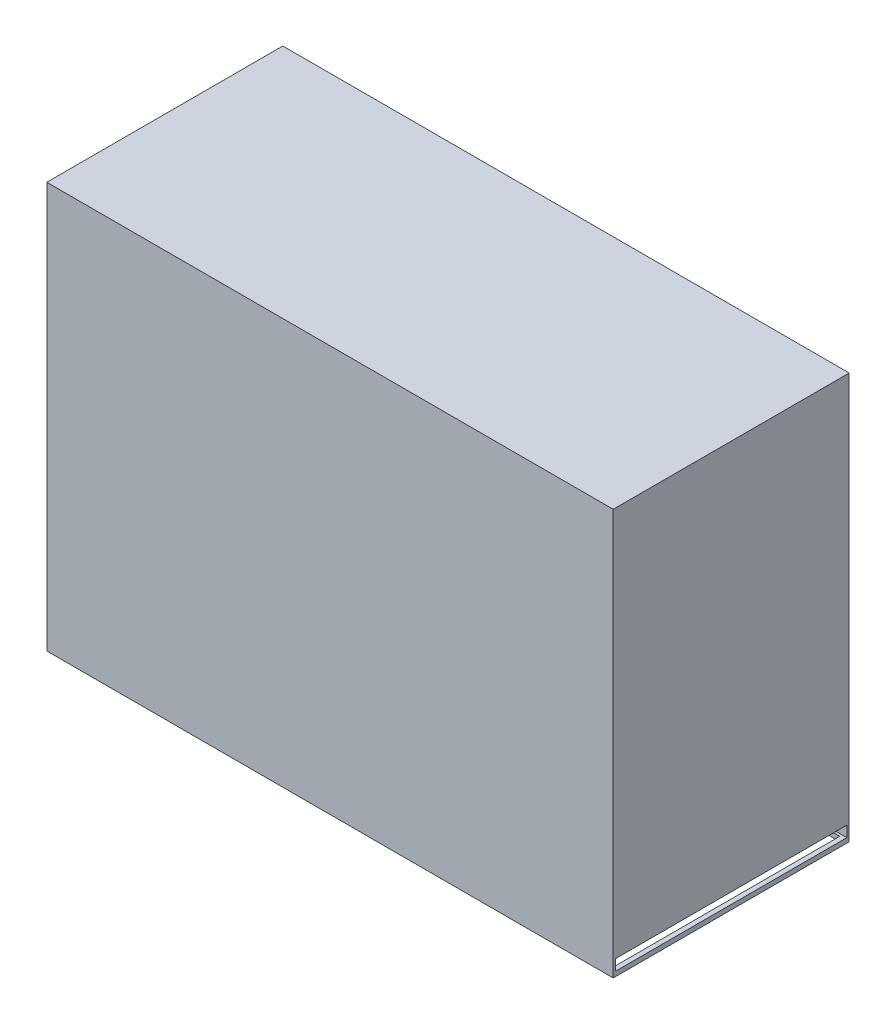
SolidWorks part; units mm, degrees
ref_plane "Piano frontale" through (0, 0, 0) normal (0, 0, 1) x (1, 0, 0)
ref_plane "Piano superiore" through (0, 0, 0) normal (0, 1, 0) x (1, 0, 0)
ref_plane "Piano destro" through (0, 0, 0) normal (1, 0, 0) x (0, 0, -1)
sketch "Schizzo1" plane through (0, 0, 0) normal (0, 0, 1) x (1, 0, 0)
  line L1 (0, 0) -> (120, 0)
  line L2 (0, 0) -> (0, 82)
  line L3 (0, 82) -> (120, 82)
  line L4 (120, 0) -> (120, 82)
  point P9 (0, 0)
  point P10 (0, 0)
  dimension "D1" = 120
  dimension "D2" = 82
extrude "Estrusione-Estrusione4" add sketch "Schizzo1" along normal blind 50
sketch "Schizzo6" plane through (0, 0, 0) normal (0, -1, 0) x (1, 0, 0)
  line L0 (0, 50) -> (120, 50) construction
  line L1 (1, 49) -> (119, 49)
  line L2 (1, 49) -> (1, 1)
  line L3 (1, 1) -> (119, 1)
  line L4 (119, 49) -> (119, 1)
  line L5 (0, 50) -> (0, 0) construction
  dimension "D1" = 48
  dimension "D2" = 118
  dimension "D3" = 1
  dimension "D4" = 1
extrude "Taglio-Estrusione2" cut sketch "Schizzo6" against normal blind 50
sketch "Schizzo7" plane through (0, 50, 0) normal (0, -1, 0) x (1, 0, 0)
  line L1 (1, 49) -> (54, 49)
  line L2 (1, 49) -> (1, 29)
  line L3 (1, 29) -> (54, 29)
  line L4 (54, 49) -> (54, 29)
  dimension "D1" = 53
  dimension "D2" = 20
extrude "Estrusione-Estrusione5" add sketch "Schizzo7" along normal blind 27
sketch "Schizzo8" plane through (0, 23, 0) normal (0, -1, 0) x (1, 0, 0)
  line L0 (1, 29) -> (54, 29) construction
  line L1 (1, 49) -> (53, 49)
  line L2 (1, 49) -> (1, 30)
  line L3 (1, 30) -> (53, 30)
  line L4 (53, 49) -> (53, 30)
  line L5 (54, 29) -> (54, 49) construction
  line L6 (1, 49) -> (1, 1) construction
  dimension "D1" = 19
  dimension "D2" = 1
  dimension "D3" = 1
  dimension "D4" = 0
extrude "Taglio-Estrusione4" cut sketch "Schizzo8" against normal blind 27 contours L2 L1 L4 L3
sketch "Schizzo9" plane through (0, 50, 0) normal (0, -1, 0) x (-1, 0, 0)
  line L0 (-114, -5) -> (-119, -5)
  line L3 (-119, -5) -> (-119, -4)
  line L6 (-114, -5) -> (-114, -4)
  line L7 (-119, -1) -> (-119, -49) construction
  line L8 (-119, -4) -> (-114, -4)
  line L9 (-114, -5) -> (-1, -5)
  line L10 (-1, -29) -> (-1, -1) construction
  line L11 (-1, -5) -> (-1, -4)
  line L12 (-1, -49) -> (-1, -1) construction
  line L13 (-1, -4) -> (-114, -4)
  line M6 (-1, -29) -> (-1, -1)
  line M8 (-119, -1) -> (-119, -49)
  dimension "D3" = 5
extrude "Estrusione-Estrusione6" add sketch "Schizzo9" along normal blind 50 contours L8 L0 L6 M8 region at (116.5, 50, 4.5)
extrude "Estrusione-Estrusione7" add sketch "Schizzo9<3>" along normal blind 1.85 contours L13 L6 L9 M6 region at (57.5, 50, 4.5)
sketch "Schizzo9<3>" plane through (0, 50, 0) normal (0, -1, 0) x (-1, 0, 0) same geometry as "Schizzo9"
sketch "Schizzo10" plane through (0, 0, 0) normal (0, -1, 0) x (1, 0, 0)
sketch "Schizzo11" plane through (0, 0, 0) normal (0, -1, 0) x (1, 0, 0)
  line L1 (0, 50) -> (120, 50)
  line L2 (0, 50) -> (0, 0)
  line L3 (0, 0) -> (120, 0)
  line L4 (120, 50) -> (120, 0)
  line L5 (1, 49) -> (119, 49)
  line L6 (1, 49) -> (1, 1)
  line L7 (1, 1) -> (119, 1)
  line L8 (119, 49) -> (119, 1)
extrude "Estrusione-Estrusione8" add sketch "Schizzo11" along normal blind 4
sketch "Schizzo13" plane through (120, 0, 0) normal (1, 0, 0) x (0, 0, -1)
  line L0 (0, -4) -> (-50, -4) construction
  line L1 (-0.5, -3) -> (-49.5, -3)
  line L2 (-0.5, -3) -> (-0.5, -0.7)
  line L3 (-0.5, -0.7) -> (-49.5, -0.7)
  line L4 (-49.5, -3) -> (-49.5, -0.7)
  line L5 (-50, -4) -> (-50, 82) construction
  line L6 (0, -4) -> (0, 82) construction
  dimension "D1" = 1
  dimension "D2" = 0.5
  dimension "D3" = 0.5
  dimension "D4" = 2.3
extrude "Taglio-Estrusione6" cut sketch "Schizzo13" against normal blind 119
